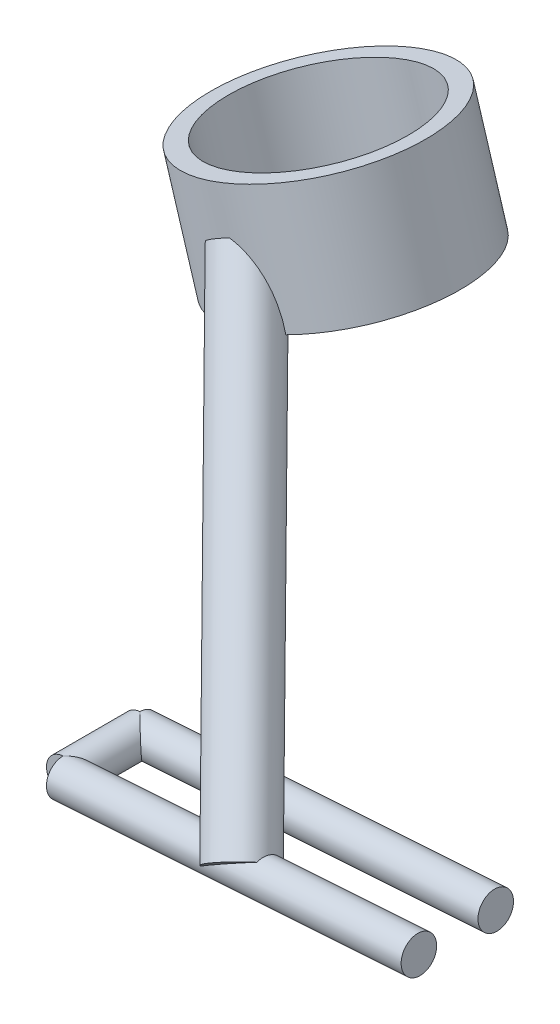
SolidWorks part; units mm, degrees
material "Acero aleado"
ref_plane "Alzado" through (0, 0, 0) normal (0, 0, 1) x (1, 0, 0)
ref_plane "Planta" through (0, 0, 0) normal (0, 1, 0) x (1, 0, 0)
ref_plane "Vista lateral" through (0, 0, 0) normal (1, 0, 0) x (0, 0, -1)
sketch3d "Sk_Abrazadera"
  line L0 (-51.165, 167.3533, 0) -> (-57.0125, 186.4794, 0)
  dimension "D1" = 20
sweep "Abrazadera" add path "Sk_Abrazadera" circular profile diameter 38 parameters "D3"=38
sketch3d "Sk_Brazo"
  line L0 (-54.0888, 176.9164, 15) -> (-20, 120, 50)
  dimension "D1" = 75.0101
sweep "Brazo" add path "Sk_Brazo" circular profile diameter 10 parameters "D3"=10
sketch3d "Sk_Placa_int"
  line L0 (-50, 118, 37) -> (10, 122, 37)
  dimension "D1" = 60.1332
sweep "Placa_int" add path "Sk_Placa_int" circular profile diameter 6 parameters "D3"=6
sketch3d "Sk_Placa_ext"
  line L0 (-50, 118, 50) -> (10, 122, 50)
  dimension "D1" = 60.1332
sweep "Placa_ext" add path "Sk_Placa_ext" circular profile diameter 6 parameters "D3"=6
sketch3d "Sk_Puente_placas"
  line L0 (-50, 118, 37) -> (-50, 118, 50)
sweep "Puente_placas" add path "Sk_Puente_placas" circular profile diameter 6 parameters "D3"=6
sketch3d "Sk_Taladro_abrazadera"
  line L0 (-49.7032, 162.5718, 0) -> (-58.4743, 191.261, 0)
  dimension "D1" = 30
sweep "Taladro_abrazadera" cut path "Sk_Taladro_abrazadera" circular profile diameter 31.8 parameters "D3"=31.8
